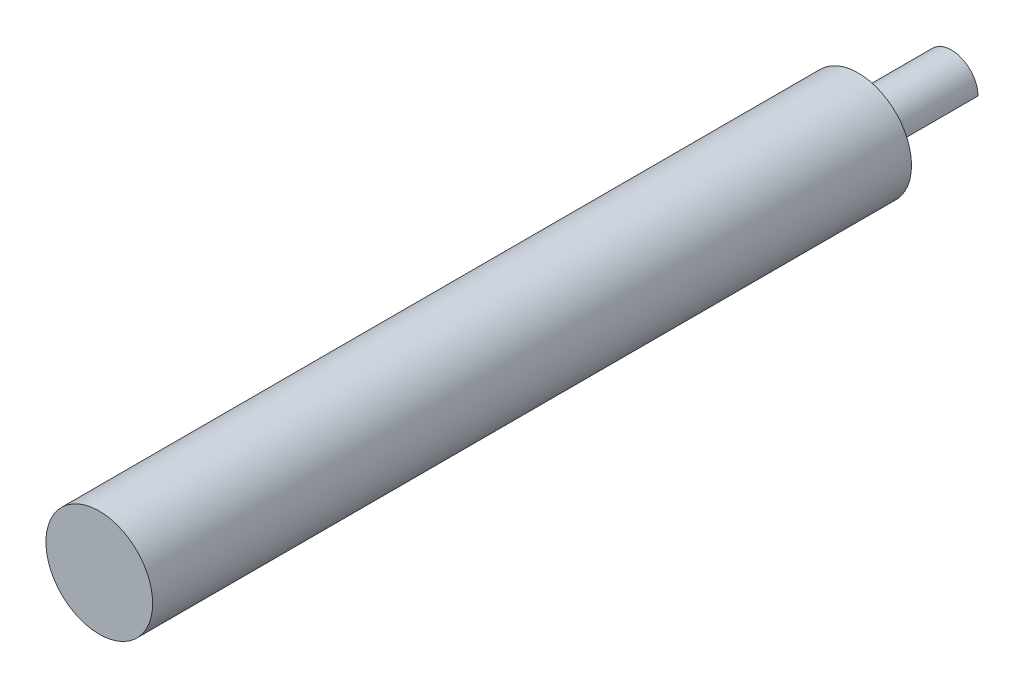
SolidWorks part; units mm, degrees
ref_plane "Front Plane" through (0, 0, 0) normal (0, 0, 1) x (1, 0, 0)
ref_plane "Top Plane" through (0, 0, 0) normal (0, 1, 0) x (1, 0, 0)
ref_plane "Right Plane" through (0, 0, 0) normal (1, 0, 0) x (0, 0, -1)
sketch "Sketch1" plane through (0, 0, 0) normal (0, 0, 1) x (1, 0, 0)
  circle A0 centre (0, 0) radius 3.1623
  dimension "D1" = 6.3246
extrude "Boss-Extrude1" add sketch "Sketch1" along normal blind 11.0998
sketch "Sketch2" plane through (0, 0, 0) normal (0, 0, -1) x (-1, 0, 0)
  line L0 (0.0012, -3.1623) -> (-3.1623, 0.0012)
  circle A0 centre (0, 0) radius 3.1623 construction
  dimension "D1" = 2.2352
extrude "Cut-Extrude1" cut sketch "Sketch2" against normal through all and the other way through all
sketch "Sketch3" plane through (0, 0, 11.0998) normal (0, 0, 1) x (1, 0, 0)
  circle A0 centre (0, 0) radius 6.35
  dimension "D1" = 12.7
extrude "Boss-Extrude2" add sketch "Sketch3" along normal blind 90.297
sketch "Sketch5" plane through (0, 0, 101.3968) normal (0, 0, 1) x (1, 0, 0)
  circle A0 centre (0, 0) radius 6.35
fillet "Fillet1" radius 1.27 2 edges at (-2.2361, 2.2361, 11.0998) (1.5805, -1.5805, 11.0998) type face fillet first side face at (6.35, 0, 11.0998) second side face at (-0.3278, 0.3278, 5.5499) second side face at (1.5805, -1.5805, 5.5499)
